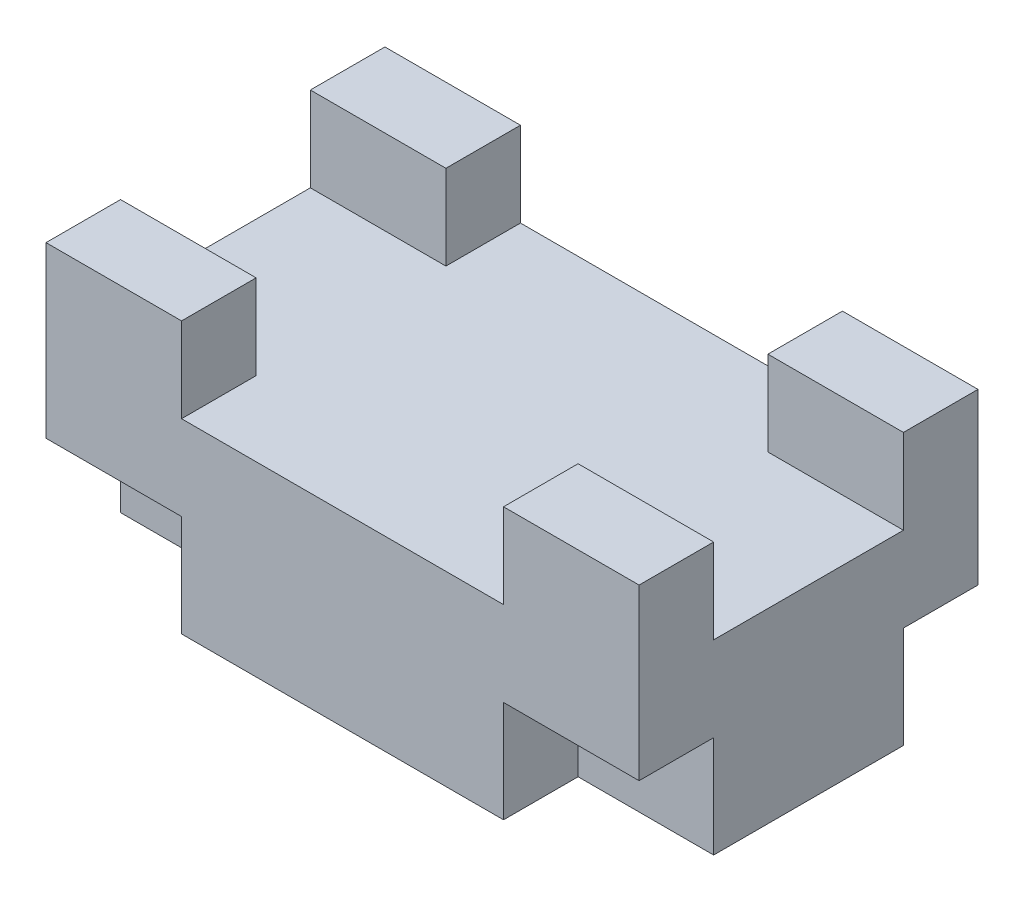
SolidWorks part; units mm, degrees
ref_plane "Front Plane" through (0, 0, 0) normal (0, 0, 1) x (1, 0, 0)
ref_plane "Top Plane" through (0, 0, 0) normal (0, 1, 0) x (1, 0, 0)
ref_plane "Right Plane" through (0, 0, 0) normal (1, 0, 0) x (0, 0, -1)
sketch "Sketch2" plane through (0, 0, 0) normal (0, 1, 0) x (1, 0, 0)
  line L1 (-87.5, -50) -> (87.5, -50)
  line L2 (-87.5, -50) -> (-87.5, 50)
  line L3 (-87.5, 50) -> (87.5, 50)
  line L4 (87.5, -50) -> (87.5, 50)
  line L5 (-87.5, -50) -> (87.5, 50) construction
  line L6 (-87.5, 50) -> (87.5, -50) construction
  line L15 (-87.5, 50) -> (-47.5, 50)
  line L16 (-87.5, 50) -> (-87.5, 28)
  line L17 (-87.5, 28) -> (-47.5, 28)
  line L18 (-47.5, 50) -> (-47.5, 28)
  line L19 (87.5, 50) -> (47.5, 50)
  line L20 (87.5, 50) -> (87.5, 28)
  line L21 (87.5, 28) -> (47.5, 28)
  line L22 (47.5, 50) -> (47.5, 28)
  line L23 (-87.5, -50) -> (-47.5, -50)
  line L24 (-87.5, -50) -> (-87.5, -28)
  line L25 (-87.5, -28) -> (-47.5, -28)
  line L26 (-47.5, -50) -> (-47.5, -28)
  line L27 (87.5, -50) -> (47.5, -50)
  line L28 (87.5, -50) -> (87.5, -28)
  line L29 (87.5, -28) -> (47.5, -28)
  line L30 (47.5, -50) -> (47.5, -28)
  point P0 (0, 0)
  dimension "D1" = 175
  dimension "D2" = 100
  dimension "D3" = 22
  dimension "D4" = 22
  dimension "D5" = 22
  dimension "D6" = 22
  dimension "D7" = 40
  dimension "D8" = 40
  dimension "D9" = 40
  dimension "D10" = 40
extrude "Boss-Extrude1" add sketch "Sketch2" along normal blind 30 contours L1 L30 L29 L4 L21 L22 L3 L18 L17 L2 L25 L26 region at (0, 0, 0)
extrude "Boss-Extrude2" add sketch "Sketch2<3>" along normal blind 25 from surface contours L1 L26 L25 L2 | L18 L3 L2 L17 | L3 L22 L21 L4 | L30 L1 L4 L29 | L1 L30 L29 L4 L21 L22 L3 L18 L17 L2 L25 L26 region at (-67.5, 0, 39) region at (0, 0, 0) region at (67.5, 0, 39) region at (-67.5, 0, -39) region at (67.5, 0, -39) starting at face at (0, 30, 0)
sketch "Sketch2<3>" plane through (0, 0, 0) normal (0, 1, 0) x (1, 0, 0) same geometry as "Sketch2"
extrude "Boss-Extrude3" add sketch "Sketch2<5>" along normal blind 25 from surface contours L1 L26 L25 L2 | L18 L3 L2 L17 | L3 L22 L21 L4 | L30 L1 L4 L29 region at (-67.5, 0, 39) region at (67.5, 0, 39) region at (-67.5, 0, -39) region at (67.5, 0, -39) starting at face at (0, 55, 0)
sketch "Sketch2<5>" plane through (0, 0, 0) normal (0, 1, 0) x (1, 0, 0) same geometry as "Sketch2"
